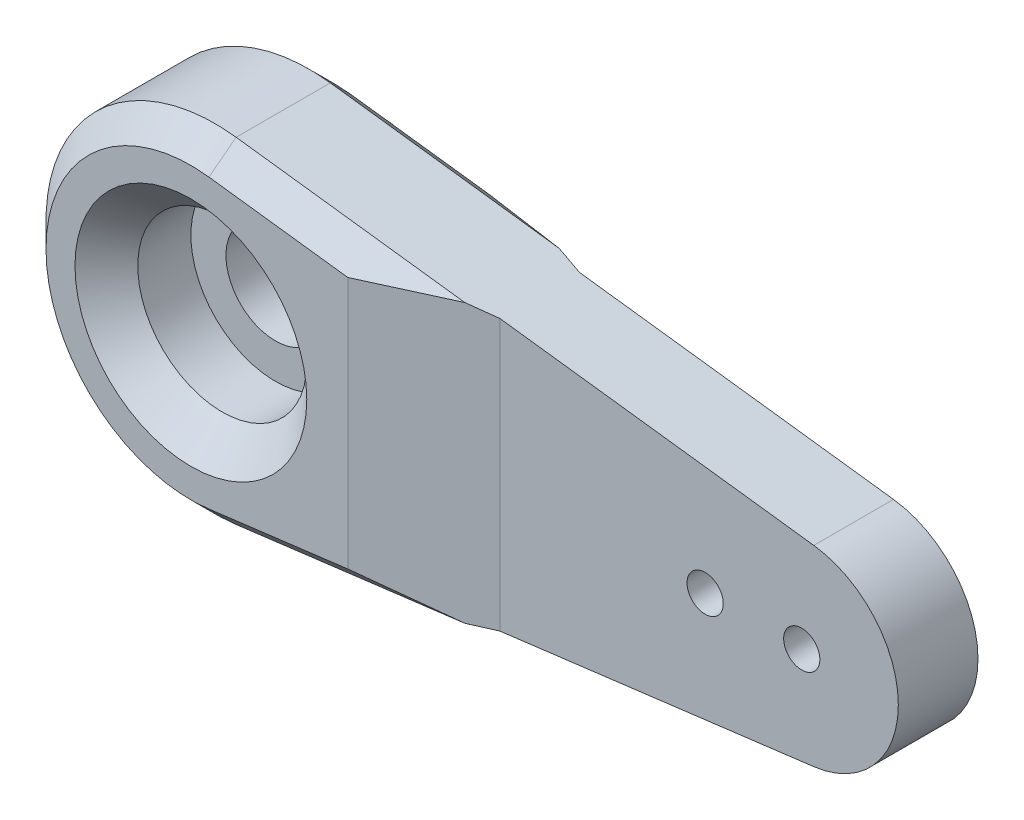
SolidWorks part; units mm, degrees
ref_plane "Plan de face" through (0, 0, 0) normal (0, 0, 1) x (1, 0, 0)
ref_plane "Plan de dessus" through (0, 0, 0) normal (0, 1, 0) x (1, 0, 0)
ref_plane "Plan de droite" through (0, 0, 0) normal (1, 0, 0) x (0, 0, -1)
sketch "Esquisse1" plane through (0, 0, 0) normal (0, 0, 1) x (1, 0, 0)
  line L0 (0, 0) -> (58.0381, 0) construction
  line L1 (0, 11.5762) -> (0, -10.9476) construction
  line L2 (24, 6.8619) -> (24, -5.6048) construction
  line L3 (0.875, 6.9451) -> (24.5, 3.9686) construction
  line L4 (24.5, -3.9686) -> (0.875, -6.9451) construction
  line L5 (0.875, 6.9451) -> (24.5, 3.9686)
  line L6 (24.5, -3.9686) -> (0.875, -6.9451)
  line L7 (-7, 0) -> (-7, 16.9861) construction
  line L8 (28, 0) -> (28, 13.2444) construction
  circle A0 centre (0, 0) radius 7 construction
  circle A1 centre (24, 0) radius 4 construction
  arc A2 (0.875, 6.9451) -> (0.875, -6.9451) centre (0, 0) ccw
  arc A3 (24.5, 3.9686) -> (24.5, -3.9686) centre (24, 0) cw
  circle A4 centre (0, 0) radius 2.0468
  dimension "D2" = 14
  dimension "D3" = 8
  dimension "D1" = 35
extrude "Boss.-Extru.1" add sketch "Esquisse1" along normal blind 3.3
sketch "Esquisse2" plane through (0, 0, 3.3) normal (0, 0, 1) x (1, 0, 0)
  line L0 (0.875, -6.9451) -> (24.5, -3.9686) construction
  line L1 (6.5, 11.5318) -> (6.5, -12.9458) construction
  line L2 (0.875, 6.9451) -> (6.5, 6.2364)
  line L3 (24.5, 3.9686) -> (0.875, 6.9451) construction
  line L4 (6.5, 6.2364) -> (6.5, -6.2364)
  line L5 (6.5, -6.2364) -> (0.875, -6.9451)
  arc A0 (0.875, 6.9451) -> (0.875, -6.9451) centre (0, 0) ccw
  circle A1 centre (0, 0) radius 2.0468
  dimension "D1" = 6.5
extrude "Boss.-Extru.2" add sketch "Esquisse2" along normal blind 1.3 and the other way offset from surface (4.6 mm away) 1.3 other way up to face at (11.5938, 0, 0)
chamfer "Chanfrein1" distance 5 distance2 1.3 1 edges at (6.5, 0, 3.3)
chamfer "Chanfrein3" distance 1.3 distance2 5 1 edges at (6.5, 0, 0)
chamfer "Chanfrein2" distance 1 angle 45 6 edges at (3.6875, 6.5908, 4.6) (3.6875, -6.5908, 4.6) (-7, 0, 4.6) (3.6875, -6.5908, -1.3) (3.6875, 6.5908, -1.3) (-7, 0, -1.3)
sketch "Esquisse3" plane through (0, 0, -1.3) normal (0, 0, -1) x (-1, 0, 0)
  circle A0 centre (0, 0) radius 5.5
  circle A1 centre (0, 0) radius 2.75
  dimension "D1" = 11
  dimension "D2" = 5.5
extrude "Boss.-Extru.3" add sketch "Esquisse3" along normal blind 1.8
chamfer "Chanfrein4" distance 1.5 angle 45 1 edges at (-5.5, 0, -3.1)
sketch "Esquisse4" plane through (0, 0, 4.6) normal (0, 0, 1) x (1, 0, 0)
  circle A0 centre (0, 0) radius 3.5
  dimension "D1" = 7
extrude "Enlèv. mat.-Extru.1" cut sketch "Esquisse4" against normal blind 3.5
chamfer "Chanfrein5" distance 1.3 angle 45 1 edges at (3.5, 0, 4.6)
sketch "Esquisse5" plane through (0, 0, 3.3) normal (0, 0, 1) x (1, 0, 0)
  line L0 (0, 0) -> (45.1885, 0) construction
  line L1 (24, 2.5592) -> (24, -2.5592) construction
  circle A0 centre (24, 0) radius 0.75
  circle A1 centre (20, 0) radius 0.75
  circle A4 centre (16, 0) radius 0.75 [skipped]
  circle A5 centre (12, 0) radius 0.75 [skipped]
  point P5 (20, 0)
  point P6 (24, 0)
  dimension "D2" = 1.5
  dimension "D1" = 24
  dimension "D4" = 4
  dimension "D3" = 4
extrude "Enlèv. mat.-Extru.2" cut sketch "Esquisse5" against normal blind 3.5
